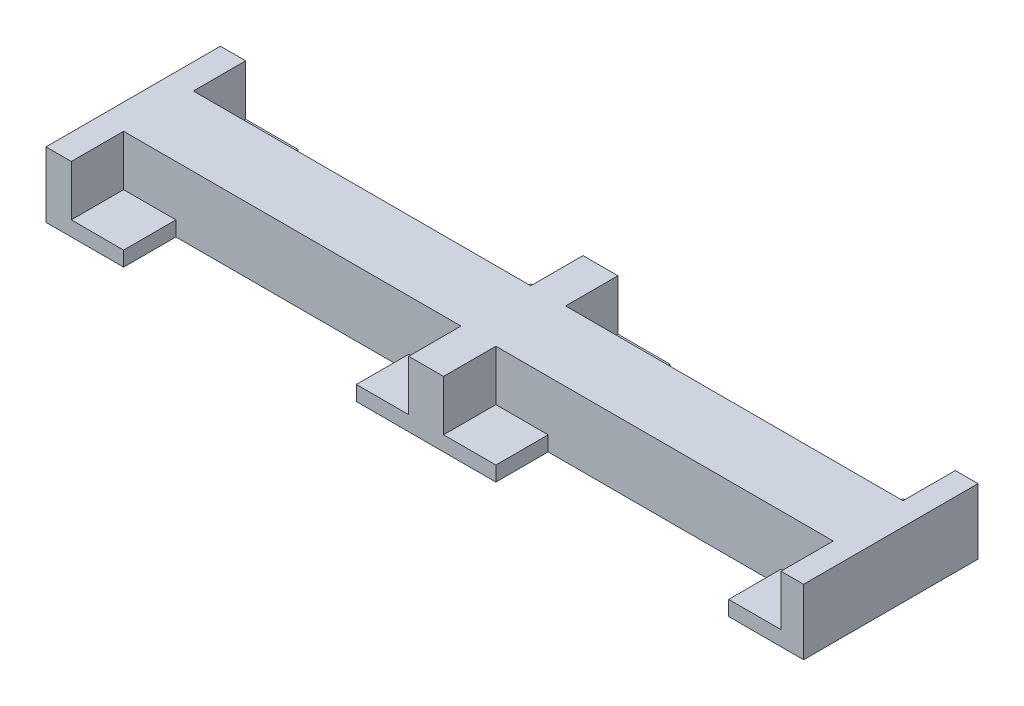
SolidWorks part; units mm, degrees
ref_plane "Front Plane" through (0, 0, 0) normal (0, 0, 1) x (1, 0, 0)
ref_plane "Top Plane" through (0, 0, 0) normal (0, 1, 0) x (1, 0, 0)
ref_plane "Right Plane" through (0, 0, 0) normal (1, 0, 0) x (0, 0, -1)
sketch "Sketch2" plane through (0, 0, 0) normal (0, 1, 0) x (1, 0, 0)
  line L1 (-250, 50) -> (184.5, 50)
  line L2 (-250, 50) -> (-250, 150)
  line L3 (-250, 150) -> (184.5, 150)
  line L4 (184.5, 50) -> (184.5, 150)
  point P0 (0, 0)
  dimension "D1" = 434.5
  dimension "D2" = 100
extrude "Boss-Extrude1" add sketch "Sketch2" along normal blind 37.5
sketch "Sketch5" plane through (0, 0, -150) normal (0, 0, -1) x (-1, 0, 0)
  line L0 (250, 37.5) -> (250, 0) construction
  line L5 (42, 66.5) -> (72, 66.5)
  line L6 (72, 66.5) -> (72, 75)
  line L7 (-184.5, 0) -> (250, 0) construction
  line L17 (72, 75) -> (205.5, 75)
  line L18 (205.5, 75) -> (205.5, 66.5)
  line L19 (205.5, 66.5) -> (235.5, 66.5)
  line L20 (235.5, 66.5) -> (235.5, 8.5)
  line L21 (235.5, 8.5) -> (205.5, 8.5)
  line L22 (205.5, 8.5) -> (205.5, 0)
  line L23 (205.5, 0) -> (72, 0)
  line L24 (72, 0) -> (72, 8.5)
  line L25 (72, 8.5) -> (42, 8.5)
  line L26 (42, 8.5) -> (42, 66.5)
  line L27 (72, 75) -> (205.5, 0) construction
  line L28 (205.5, 75) -> (72, 0) construction
  point P18 (138.75, 37.5)
  dimension "D1" = 133.5
  dimension "D2" = 8.5
  dimension "D3" = 0
  dimension "D4" = 30
  dimension "D5" = 30
  dimension "D6" = 14.5
  dimension "D8" = 37.5
extrude "Cut-Extrude3" cut sketch "Sketch5" against normal blind 30
ref_plane "Plane1" through (0, 0, -100) normal (0, 0, 1) x (1, 0, 0)
pattern_linear "LPattern1" count 2 spacing 213.5 along (1, 0, 0) of "Cut-Extrude3"
mirror "Mirror1" about plane through (0, 0, -100) normal (0, 0, 1) of "LPattern1", "Cut-Extrude3"
